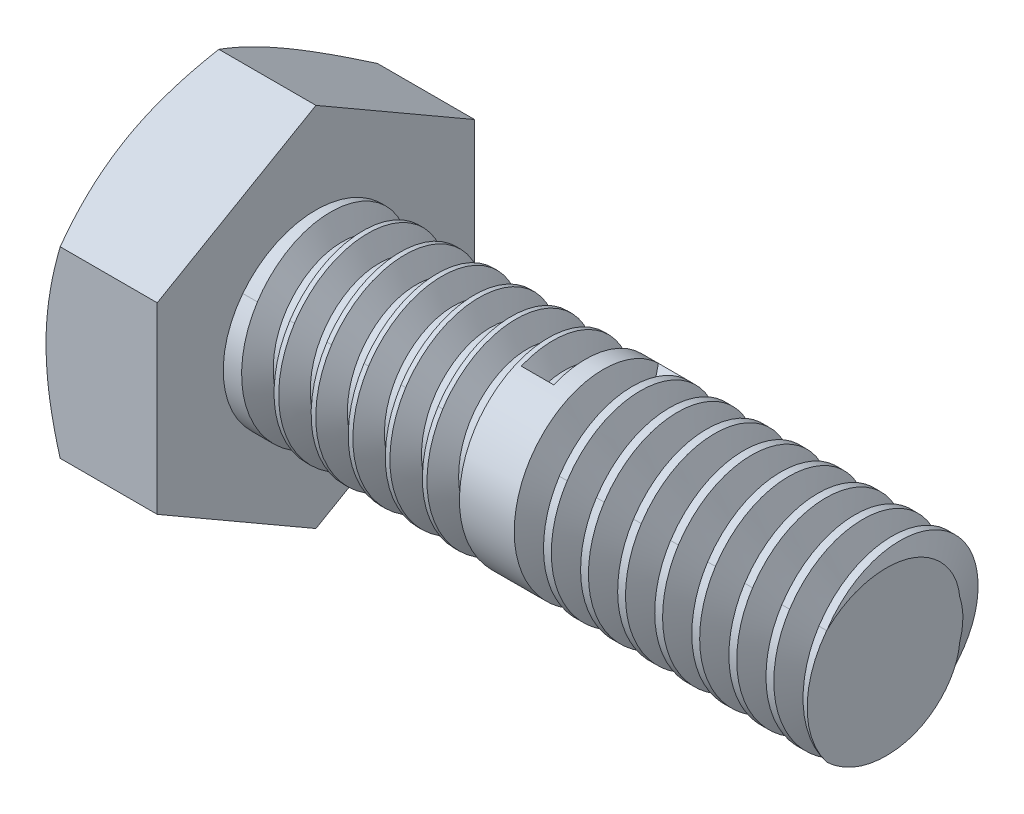
SolidWorks part; units mm, degrees
ref_plane "Front Plane" through (0, 0, 0) normal (0, 0, 1) x (1, 0, 0)
ref_plane "Top Plane" through (0, 0, 0) normal (0, 1, 0) x (1, 0, 0)
ref_plane "Right Plane" through (0, 0, 0) normal (1, 0, 0) x (0, 0, -1)
sketch "Sketch1" plane through (0, 0, 0) normal (1, 0, 0) x (0, 0, -1)
  line L1 (5.4356, 3.1382) -> (0, 6.2765)
  line L2 (0, 6.2765) -> (-5.4356, 3.1382)
  line L3 (-5.4356, 3.1382) -> (-5.4356, -3.1382)
  line L4 (-5.4356, -3.1382) -> (0, -6.2765)
  line L5 (0, -6.2765) -> (5.4356, -3.1382)
  line L6 (5.4356, -3.1382) -> (5.4356, 3.1382)
  circle A0 centre (0, 0) radius 5.4356 construction
  dimension "A" = 10.8712
extrude "Boss-Extrude1" add sketch "Sketch1" along normal blind 3.81
sketch "Sketch2" plane through (0, 0, 0) normal (0, 0, 1) x (1, 0, 0)
  line L0 (0, 0) -> (12.1777, 0) construction
  line L1 (0, 6.2765) -> (0, 5.4356)
  line L2 (0, 6.2765) -> (0, 3.1382) construction
  line L3 (0, 5.4356) -> (0.4855, 6.2765)
  line L4 (3.81, 6.2765) -> (0, 6.2765) construction
  line L5 (0.4855, 6.2765) -> (0, 6.2765)
  dimension "D1" = 30
  dimension "D2" = 10.8712
revolve "Cut-Revolve1" cut sketch "Sketch2" angle 360 about L0
sketch "Sketch3" plane through (3.81, 0, 0) normal (1, 0, 0) x (0, 0, -1)
  circle A0 centre (0, 0) radius 3.175
  dimension "D1" = 6.35
extrude "Boss-Extrude2" add sketch "Sketch3" along normal blind 20
sketch "Sketch4" plane through (23.81, 0, 0) normal (1, 0, 0) x (0, 0, -1)
  circle A1 centre (0, 0) radius 3.175 construction
  circle A2 centre (0, 0) radius 3.175
curve "Helix/Spiral1" pitch 1.27 height 10 radius 3.175 centre (23.81, 0, 0) axis (-1, 0, 0) start towards (0, 0, -1)
sketch "Sketch5" plane through (0, 0, 0) normal (0, 1, 0) x (1, 0, 0)
  line L0 (23.2766, 3.2512) -> (23.7465, 2.159)
  line L1 (23.7465, 2.159) -> (23.8735, 2.159)
  line L2 (23.81, 2.159) -> (23.81, 3.2512) construction
  line L3 (24.3434, 3.2512) -> (23.2766, 3.2512)
  line L4 (24.3434, 3.2512) -> (23.8735, 2.159)
  line L5 (23.5116, 2.7051) -> (23.0734, 2.7051) construction
  line L6 (0, 0) -> (28.998, 0) construction
  point P6 (23.81, 3.175)
  dimension "D1" = 0.0762
  dimension "D2" = 1.0668
  dimension "D3" = 0.127
  dimension "D4" = 5.4102
sweep "Cut-Sweep1" cut profiles "Sketch5" path "Helix/Spiral1" align with end faces yes
thread "Thread2" pitch 1.27 method cut profile "Thread Profile1" start angle 0, offset 0, length 8, pitch 1.27, diameter 6.35
ref_plane "Plane1" through (3.81, 0, -3.175) normal (0, -1, 0) x (0, 0, -1)
sketch "Thread Profile1" plane through (3.81, 0, -3.175) normal (0, -1, 0) x (0, 0, -1)
  line L0 (0, 0) -> (0, 1.27) construction
  line L11 (0, 0) -> (0, 1.1112)
  line L12 (0, 1.1112) -> (-0.6874, 0.7144)
  line L13 (-0.6874, 0.7144) -> (-0.6874, 0.3969)
  line L15 (-0.6874, 0.3969) -> (0, 0)
  line L17 (-0.6874, 0.5556) -> (0, 0.5556) construction
  point P2 (0, 0)
  dimension "Pitch" = 1.27
  dimension "Profile_Angle" = 60
  dimension "Profile_Land" = 0.3175
  dimension "Profile_Height" = 0.6874
equation "\"D2@Sketch2\"=\"A@Sketch1\""
